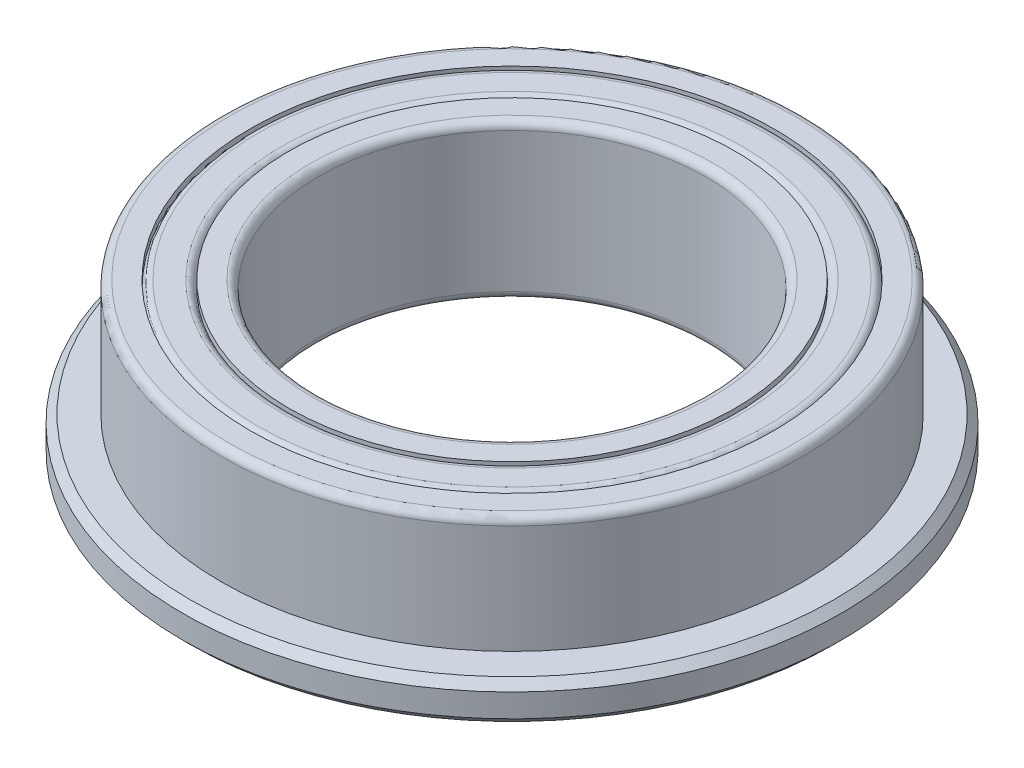
SolidWorks part; units mm, degrees
ref_plane "前视基准面" through (0, 0, 0) normal (0, 0, 1) x (1, 0, 0)
ref_plane "上视基准面" through (0, 0, 0) normal (0, 1, 0) x (1, 0, 0)
ref_plane "右视基准面" through (0, 0, 0) normal (1, 0, 0) x (0, 0, -1)
sketch "草图1" plane through (0, 0, 0) normal (0, 1, 0) x (1, 0, 0)
  circle A0 centre (0, 0) radius 5
  circle A1 centre (0, 0) radius 7.5
  circle A2 centre (0, 0) radius 8.5
  circle A3 centre (0, 0) radius 5.75
  circle A4 centre (0, 0) radius 6.75
extrude "凸台-拉伸1" add sketch "草图1" along normal blind 4 contours A4 A3 region at (-6.5591, 0, 0)
extrude "凸台-拉伸2" add sketch "草图1<3>" along normal blind 4 separate body contours A1 A4 | A3 A0 region at (-7.2879, 0, 0) region at (-5.5874, 0, 0)
sketch "草图1<3>" plane through (0, 0, 0) normal (0, 1, 0) x (1, 0, 0) same geometry as "草图1"
extrude "凸台-拉伸3" add sketch "草图1<4>" along normal blind 1 separate body contours A2 A1 region at (-8.2596, 0, 0)
sketch "草图1<4>" plane through (0, 0, 0) normal (0, 1, 0) x (1, 0, 0) same geometry as "草图1"
fillet "圆角1" radius 0.2 4 edges at (0, 0, 6.75) (0, 0, 5.75) (0, 4, 6.75) (0, 4, 5.75)
fillet "圆角2" radius 0.2 2 edges at (0, 0, 5) (0, 4, 5)
chamfer "倒角1" distance 0.2 angle 45 2 edges at (0, 1, 8.5) (0, 0, 8.5)
fillet "圆角4" radius 0.2 1 edges at (0, 4, 7.5)
